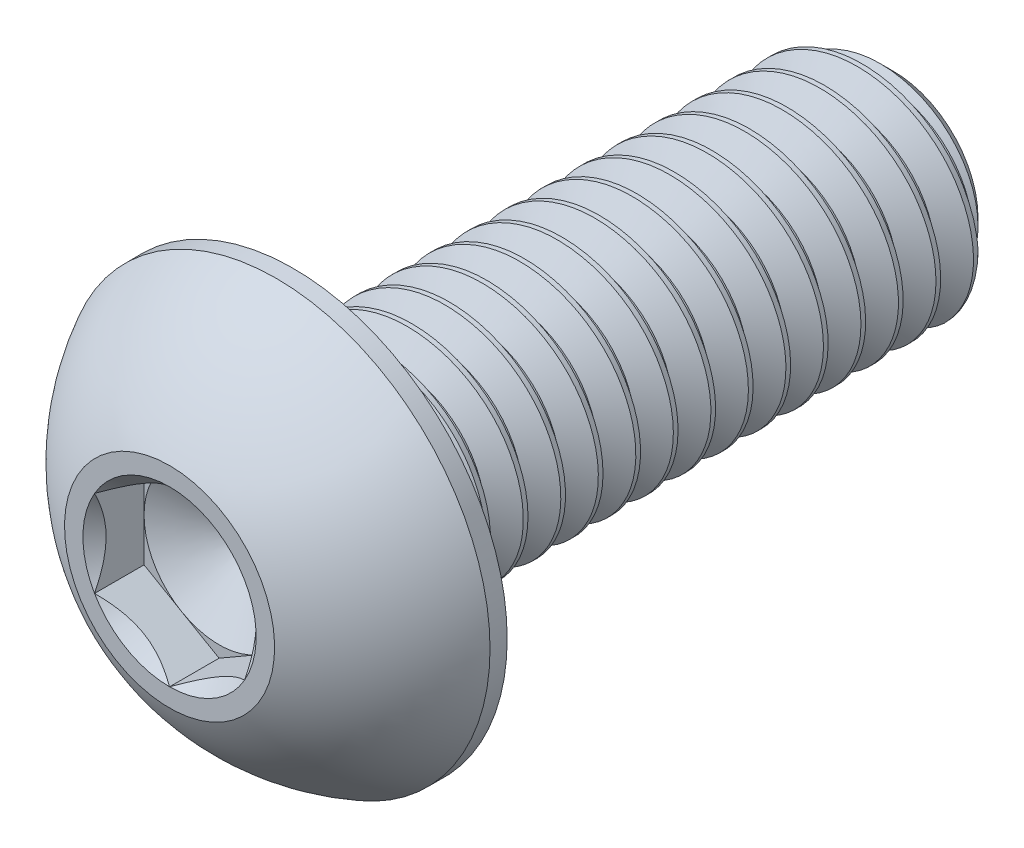
SolidWorks part; units mm, degrees
ref_plane "Front Plane" through (0, 0, 0) normal (0, 0, 1) x (1, 0, 0)
ref_plane "Top Plane" through (0, 0, 0) normal (0, 1, 0) x (1, 0, 0)
ref_plane "Right Plane" through (0, 0, 0) normal (1, 0, 0) x (0, 0, -1)
sketch "Sketch1" plane through (0, 0, 0) normal (1, 0, 0) x (0, 0, -1)
  line L0 (-4.825, 0) -> (4.825, 0) construction
  line L1 (-3.175, 2.85) -> (-3.175, -2.85) construction
  line L2 (-4.825, 1) -> (-4.825, -1) construction
  line L3 (4.825, 1.5) -> (4.825, -1.5) construction
  line L4 (4.7937, 1.5541) -> (5.0437, 1.1211) construction
  line L5 (5.0437, 1.1211) -> (5.2937, 1.5541) construction
  line L6 (5.2937, 1.5541) -> (4.7937, 1.5541) construction
  line L7 (5.0437, 1.5541) -> (5.0437, 1.5) construction
  line L8 (5.0437, 1.1211) -> (5.0437, 1.1752) construction
  line L9 (5.0125, 1.1752) -> (5.075, 1.1752)
  line L10 (-4.825, 1.4) -> (-4.825, -1.4) construction
  line L11 (-3.175, 2.85) -> (-3.4036, 2.85) construction
  line L12 (-4.825, 1) -> (-4.165, 1) construction
  line L13 (-4.165, 1) -> (-3.5876, 0) construction
  point P5 (-3.175, 0)
  point P10 (3.075, -1.5)
  dimension "Drive Size" = 2
  dimension "Head Diameter" = 5.7
  dimension "Head Height" = 1.65
  dimension "Thread Size" = 3
  dimension "Length" = 8
  dimension "Thread Note" = 1.75
  dimension "Pitch" = 0.5
  dimension "Pitch/8" = 0.0625
  dimension "Approx Head Face Flat" = 2.8
  dimension "Approx Head Edge Flat" = 0.2286
  dimension "Drive Drill Clearance" = 60
  dimension "Approx Drive Depth" = 0.66
sketch "Sketch2" plane through (0, 0, 0) normal (1, 0, 0) x (0, 0, -1)
  line L0 (-4.825, 1) -> (-4.825, 1.4)
  line L1 (-3.4036, 2.85) -> (-3.175, 2.85)
  line L2 (-3.175, 2.85) -> (-3.175, 1.5)
  line L3 (-3.175, 2.85) -> (-3.175, -2.85) construction
  line L4 (-3.175, 1.5) -> (4.45, 1.5)
  line L5 (4.825, 1.125) -> (4.825, 0)
  line L6 (-4.825, 1) -> (-4.165, 1)
  line L7 (-4.165, 1) -> (-3.5876, 0)
  line L8 (4.825, 0) -> (-3.5876, 0)
  line L9 (4.45, 1.5) -> (4.825, 1.125)
  line L10 (4.45, -1.5) -> (4.45, 1.5) construction
  arc A0 (-3.4036, 2.85) -> (-4.825, 1.4) centre (-1.9466, 0) ccw
  point P13 (4.825, 1.5)
  point P25 (4.45, 0)
  dimension "D1" = 0.375
  dimension "D2" = 45
revolve "Revolve1" add sketch "Sketch2" angle 360 about L0
sketch "Sketch3" plane through (0, 0, 0) normal (0, 0, 1) x (1, 0, 0)
  line L1 (0, 1.1547) -> (-1, 0.5774)
  line L2 (-1, 0.5774) -> (-1, -0.5774)
  line L3 (-1, -0.5774) -> (0, -1.1547)
  line L4 (0, -1.1547) -> (1, -0.5774)
  line L5 (1, -0.5774) -> (1, 0.5774)
  line L6 (1, 0.5774) -> (0, 1.1547)
  circle A0 centre (0, 0) radius 1 construction
  circle A1 centre (0, 0) radius 2.85 construction
extrude "Cut-Extrude1" cut sketch "Sketch3" along normal through all from vertex starting at point (0, 1, 4.165)
sketch "Sketch4" plane through (0, 0, 4.825) normal (0, 0, 1) x (1, 0, 0)
  circle A0 centre (0, 0) radius 1.1547
extrude "Cut-Extrude2" cut sketch "Sketch4" against normal up to next (9.65 mm away) draft 45
sketch "Sketch9" plane through (0, 0, 0) normal (1, 0, 0) x (0, 0, -1)
  line L0 (4.825, -1.5) -> (-3.175, -1.5) construction
  line L1 (-3.175, -1.5) -> (4.45, -1.5) construction
  line L2 (4.825, -1.125) -> (4.825, 1.125) construction
  line L3 (-3.175, -1.5) -> (-3.175, 1.5) construction
  point P9 (4.075, -1.5)
  dimension "D1" = 0.75
sketch "Sketch5" plane through (0, 0, -4.825) normal (0, 0, -1) x (-1, 0, 0)
  circle A0 centre (0, 0) radius 1.5
split "Split1" [suppressed] bodies to split 104
curve "Helix/Spiral1" pitch 0.5 height 8.5 radius 1.5 centre (0, 0, -4.825) axis (0, 0, 1) start towards (0, 1, 0)
sketch "Sketch6" plane through (0, 0, 0) normal (1, 0, 0) x (0, 0, -1)
  line L0 (4.8094, 1.5271) -> (5.2781, 1.5271)
  line L1 (5.2781, 1.5271) -> (5.075, 1.1752)
  line L2 (5.0125, 1.1752) -> (5.075, 1.1752)
  line L3 (5.0125, 1.1752) -> (4.8094, 1.5271)
  line L4 (5.0437, 1.1211) -> (5.2937, 1.5541) construction
  line L5 (5.0437, 1.5541) -> (5.0437, 1.5) construction
  point P11 (5.0437, 1.5271)
sweep "Cut-Sweep1" cut profiles "Sketch6" path "Helix/Spiral1" align with end faces yes
sketch "Sketch10" [suppressed] plane through (0, 0, 26.4) normal (0, 0, -1) x (-1, 0, 0)
  circle A0 centre (0, 0) radius 2.002
  circle A1 centre (0, 0) radius 2 construction
  dimension "D1" = 0.002
extrude "Boss-Extrude1" [suppressed] add sketch "Sketch10"
equation "\"Pitch/8@Sketch1\" = \"Pitch@Sketch1\" * .125"
equation "\"Thread Note@Sketch1\" = \"Pitch@Sketch1\" * 3.5"
equation "\"Approx Head Face Flat@Sketch1\" = \"Drive Size@Sketch1\" * 1.4"
equation "\"Approx Head Edge Flat@Sketch1\" =  ( \"Approx Head Face Flat@Sketch1\" - \"Drive Size@Sketch1\" )  / 3.5"
equation "\"Approx Drive Depth@Sketch1\" = \"Head Height@Sketch1\" * .40"
equation "\"D1@Sketch2\"=\"Pitch@Sketch1\"*.750"
equation "\"D4@Helix/Spiral1\"=\"Pitch@Sketch1\""
equation "\"D3@Helix/Spiral1\" = \"D4@Helix/Spiral1\" + \"Length@Sketch1\""
equation "\"D1@Sketch9\"=\"Pitch@Sketch1\"*1.5"
